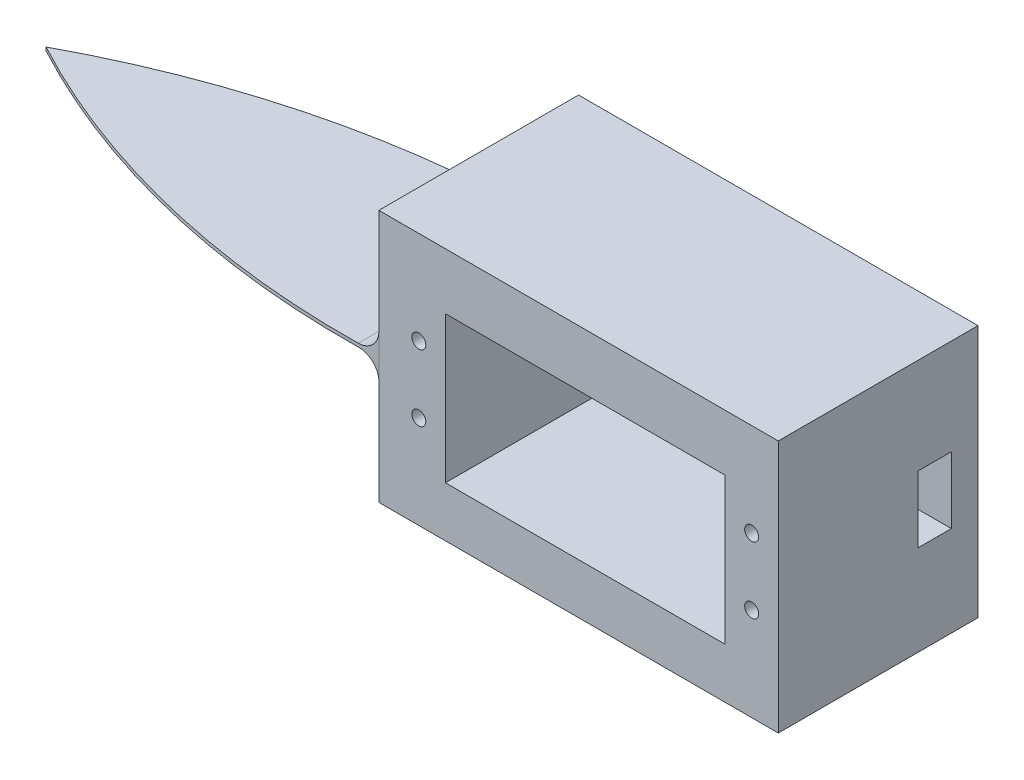
SolidWorks part; units mm, degrees
ref_plane "前基準面" through (0, 0, 0) normal (0, 0, 1) x (1, 0, 0)
ref_plane "上基準面" through (0, 0, 0) normal (0, 1, 0) x (1, 0, 0)
ref_plane "右基準面" through (0, 0, 0) normal (1, 0, 0) x (0, 0, -1)
sketch "Sketch1" plane through (0, 0, 0) normal (0, 0, 1) x (1, 0, 0)
  line L0 (-6.25, 8.6396) -> (-20.0428, 6.2396)
  line L1 (-23.0292, 3.6396) -> (-4.1228, 3.6396) construction
  line L2 (-20.0428, 1.0396) -> (-6.25, -1.3604)
  line L3 (2.0392, 8.6396) -> (15.8319, 6.2396)
  line L4 (2.0392, -1.3604) -> (15.8319, 1.0396)
  arc A0 (-6.25, 8.6396) -> (2.0392, 8.6396) centre (-2.1054, 3.6637) cw
  arc A1 (-6.25, -1.3604) -> (2.0392, -1.3604) centre (-2.1054, 3.6156) ccw
  arc A2 (15.8319, 6.2396) -> (15.8319, 1.0396) centre (15.2246, 3.6396) cw
  arc A3 (-20.0428, 6.2396) -> (-20.0428, 1.0396) centre (-19.4354, 3.6396) ccw
  point P15 (-2.1054, 10.1396)
  point P16 (-2.1054, -2.8604)
  point P19 (-22.1054, 3.6396)
  point P20 (17.8946, 3.6396)
  dimension "D6" = 2.6
  dimension "D8" = 2.67
  dimension "D9" = 13
  dimension "D10" = 40
  dimension "D1" = 2.6
  dimension "D2" = 14
  dimension "D3" = 5
  dimension "D4" = 2.6
  dimension "D5" = 5
  dimension "D7" = 2.6
sketch "Sketch2" plane through (0, 0, 0) normal (0, 0, 1) x (1, 0, 0)
  line L0 (23.733, 11.6396) -> (23.733, -4.3604)
  line L1 (23.733, -4.3604) -> (-21.267, -4.3604)
  line L2 (23.733, 11.6396) -> (-21.267, 11.6396)
  line L3 (23.733, 3.6396) -> (-8.6262, 3.6396) construction
  line L4 (-23.0292, 3.6396) -> (-4.1228, 3.6396) construction
  arc A0 (-21.267, 11.6396) -> (-21.267, -4.3604) centre (-19.3779, 3.6396) ccw
  dimension "D2" = 8.22
  dimension "D1" = 16
  dimension "D3" = 45
extrude "Boss-Extrude1" add sketch "Sketch2" along normal blind 4
extrude "Cut-Extrude1" cut sketch "Sketch1" along normal blind 3
sketch "Sketch5" plane through (23.733, 0, 0) normal (1, 0, 0) x (0, 0, -1)
  line L0 (-4, 11.6396) -> (45, 11.6396)
  line L1 (-4, -4.3604) -> (45, -4.3604)
  line L2 (-4, 11.6396) -> (-4, -4.3604)
  line L3 (45, 11.6396) -> (45, -4.3604)
  dimension "D1" = 49
  dimension "D2" = 16
extrude "Boss-Extrude2" add sketch "Sketch5" along normal blind 4
sketch "Sketch6" plane through (0, 0, -45) normal (0, 0, -1) x (-1, 0, 0)
  line L0 (-83.733, 3.6396) -> (-23.733, 3.6396) construction
  line L4 (-30.9462, -15.3604) -> (-83.733, -15.3604)
  line L5 (-83.733, -15.3604) -> (-83.733, 22.6396)
  line L6 (-23.733, 22.6396) -> (-23.733, -15.3604)
  line L8 (-23.733, -15.3604) -> (-30.9462, -15.3604)
  line L9 (-23.733, 22.6396) -> (-83.733, 22.6396)
  line L10 (-23.733, -4.3604) -> (-23.733, 11.6396) construction
  arc A0 (21.267, -4.3604) -> (21.267, 11.6396) centre (19.3779, 3.6396) ccw construction
  point P13 (27.5979, 3.6396)
  dimension "D1" = 60
  dimension "D2" = 0
  dimension "D3" = 38
  dimension "D4" = 0
extrude "Boss-Extrude15" add sketch "Sketch6" against normal blind 30
sketch "Sketch20" plane through (0, 0, 3) normal (0, 0, -1) x (-1, 0, 0)
  line L0 (-17.8946, 3.6396) -> (22.1054, 3.6396) construction
  line L1 (2.1054, 10.1396) -> (2.1054, -2.8604) construction
  circle A0 centre (2.1054, 3.6396) radius 2.4
  arc A1 (-15.8319, 6.2396) -> (-15.8319, 1.0396) centre (-15.2246, 3.6396) ccw construction
  arc A2 (20.0428, 1.0396) -> (20.0428, 6.2396) centre (19.4354, 3.6396) ccw construction
  arc A3 (6.25, 8.6396) -> (-2.0392, 8.6396) centre (2.1054, 3.6637) ccw construction
  arc A4 (-2.0392, -1.3604) -> (6.25, -1.3604) centre (2.1054, 3.6156) ccw construction
extrude "Cut-Extrude26" cut sketch "Sketch20" against normal blind 1
fillet "Fillet8" radius 4 1 edges at (23.733, 3.6396, 0) type face fillet first side face at (-0.3497, 3.6396, 0) second side face at (23.733, 3.6396, -18.75)
fillet "Fillet12" radius 4 1 edges at (27.733, 3.6396, 4) type face fillet first side face at (-4.5054, 3.6396, 4) second side face at (27.733, 3.6396, -5.5)
sketch "草圖5" plane through (0, 0, -15) normal (0, 0, 1) x (1, 0, 0)
  line L0 (27.733, 3.1939) -> (83.733, 3.1939) construction
  line L2 (27.733, 11.6396) -> (27.733, -4.3604) construction
  line L3 (83.733, 22.6396) -> (83.733, -15.3604) construction
  line L7 (75.733, -7.8061) -> (75.733, 14.1939)
  line L8 (33.733, 3.1939) -> (33.733, 14.1939)
  line L9 (33.733, 14.1939) -> (75.733, 14.1939)
  line L10 (33.733, 3.1939) -> (33.733, -7.8061)
  line L11 (33.733, -7.8061) -> (75.733, -7.8061)
  dimension "D1" = 6
  dimension "D2" = 22
  dimension "D3" = 42
extrude "除料-伸長8" cut sketch "草圖5" against normal blind 28
sketch "草圖6" plane through (0, 0, -15) normal (0, 0, 1) x (1, 0, 0)
  line L0 (27.733, 3.6396) -> (83.733, 3.6396) construction
  line L1 (27.733, 11.6396) -> (27.733, -4.3604) construction
  line L2 (83.733, 22.6396) -> (83.733, -15.3604) construction
  line L3 (33.733, 14.1939) -> (33.733, -7.8061) construction
  line L4 (75.733, -7.8061) -> (75.733, 14.1939) construction
  circle A0 centre (29.733, 8.6396) radius 1.05
  circle A1 centre (29.733, -1.3604) radius 1.05
  circle A2 centre (79.733, 8.6396) radius 1.05
  circle A3 centre (79.733, -1.3604) radius 1.05
  dimension "D1" = 10
  dimension "D2" = 4
  dimension "D3" = 10
  dimension "D4" = 5
  dimension "D5" = 5
  dimension "D6" = 4
  dimension "D7" = 4
extrude "除料-伸長9" cut sketch "草圖6" against normal blind 20
sketch "草圖8" plane through (83.733, 0, 0) normal (1, 0, 0) x (0, 0, -1)
  line L0 (45, 3.2386) -> (15, 3.2386) construction
  line L1 (45, 22.6396) -> (45, -15.3604) construction
  line L2 (15, 22.6396) -> (15, -15.3604) construction
  line L4 (42, -1.7614) -> (36, -1.7614)
  line L5 (42, -1.7614) -> (42, 8.2386)
  line L6 (42, 8.2386) -> (36, 8.2386)
  line L7 (36, -1.7614) -> (36, 8.2386)
  dimension "D1" = 3
  dimension "D2" = 9
  dimension "D3" = 5
  dimension "D4" = 5
extrude "除料-伸長10" cut sketch "草圖8" against normal blind 8
extrude "Boss-Extrude14" add sketch "Sketch6<2>" against normal blind 4
sketch "Sketch6<2>" plane through (0, 0, -45) normal (0, 0, -1) x (-1, 0, 0) same geometry as "Sketch6"
sketch "Sketch21" plane through (0, 0, 4) normal (0, 0, 1) x (1, 0, 0)
  line L0 (-21.267, 11.6396) -> (23.733, 11.6396)
  line L1 (23.733, 11.6396) -> (27.733, 11.6396)
  line L2 (27.733, 11.6396) -> (27.733, -4.3604)
  line L3 (27.733, -4.3604) -> (-21.267, -4.3604)
  line L4 (-21.267, -4.3604) -> (-27.5979, -4.3604)
  line L5 (-27.5979, -4.3604) -> (-27.5979, 3.6396)
  line L6 (-27.5979, 3.6396) -> (-27.5979, 11.6396)
  line L7 (-27.5979, 11.6396) -> (-21.267, 11.6396)
  arc A0 (-21.267, 11.6396) -> (-21.267, -4.3604) centre (-19.3779, 3.6396) ccw construction
extrude "Cut-Extrude27" cut sketch "Sketch21" against normal blind 19
sketch "Sketch26" plane through (0, 22.6396, 0) normal (0, 1, 0) x (1, 0, 0)
  line L0 (23.733, 30) -> (-41.267, 30) construction
  line L1 (23.733, 15) -> (23.733, 45) construction
  line L2 (23.733, 45) -> (23.733, 15)
  arc A0 (23.733, 45) -> (-41.267, 30) centre (18.7877, -81.9037) ccw
  arc A1 (23.733, 15) -> (-41.267, 30) centre (18.7877, 141.9037) cw
  dimension "D1" = 65
extrude "Boss-Extrude16" add sketch "Sketch26" against normal blind 19.25
extrude "Cut-Extrude28" cut sketch "Sketch26<2>" against normal blind 18.75
sketch "Sketch26<2>" plane through (0, 22.6396, 0) normal (0, 1, 0) x (1, 0, 0) same geometry as "Sketch26"
fillet "Fillet13" radius 3 1 edges at (23.733, 3.3896, -30) type face fillet first side face at (1.3981, 3.3896, -30) second side face at (23.733, -5.9854, -30)
fillet "Fillet14" radius 3 1 edges at (23.733, 3.8896, -30) type face fillet first side face at (1.3981, 3.8896, -30) second side face at (23.733, 13.2646, -30)
